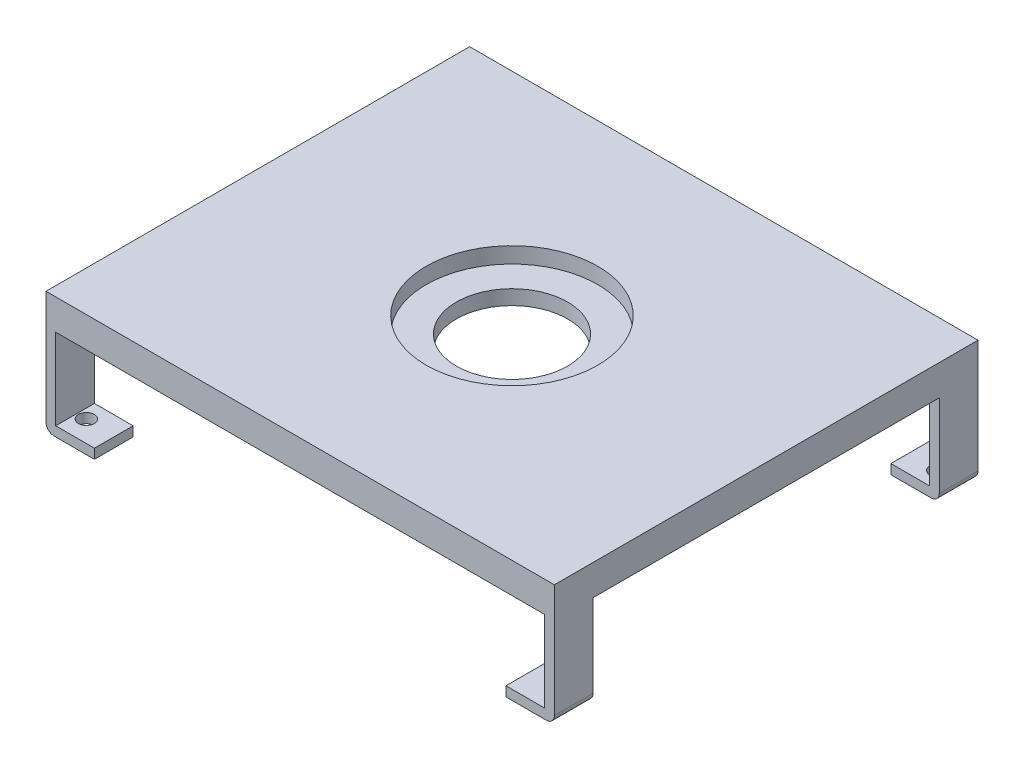
SolidWorks part; units mm, degrees
ref_plane "Plan de face" through (0, 0, 0) normal (0, 0, 1) x (1, 0, 0)
ref_plane "Plan de dessus" through (0, 0, 0) normal (0, 1, 0) x (1, 0, 0)
ref_plane "Plan de droite" through (0, 0, 0) normal (1, 0, 0) x (0, 0, -1)
sketch "Esquisse2" plane through (0, 0, 0) normal (0, 0, 1) x (1, 0, 0)
  line L0 (-64.77, 0) -> (-80.01, 0)
  line L1 (-80.01, 0) -> (-80.01, 36.2)
  line L2 (-80.01, 36.2) -> (80.01, 36.2)
  line L3 (80.01, 36.2) -> (80.01, 0)
  line L4 (80.01, 0) -> (64.77, 0)
  line L5 (64.77, 0) -> (64.77, 3.048)
  line L6 (64.77, 3.048) -> (76.962, 3.048)
  line L7 (76.962, 3.048) -> (76.962, 28.58)
  line L8 (76.962, 28.58) -> (-76.962, 28.58)
  line L9 (-76.962, 28.58) -> (-76.962, 3.048)
  line L10 (-76.962, 3.048) -> (-64.77, 3.048)
  line L11 (-64.77, 3.048) -> (-64.77, 0)
  point P12 (0, 36.2)
  dimension "D1" = 160.02
  dimension "D2" = 36.2
  dimension "D3" = 7.62
  dimension "D4" = 3.048
  dimension "D5" = 3.048
  dimension "D6" = 15.24
extrude "Boss.-Extru.1" add sketch "Esquisse2" along normal blind 133.35
sketch "Esquisse3" plane through (-80.01, 0, 0) normal (-1, 0, 0) x (0, 0, 1)
  line L0 (133.35, 0) -> (0, 0) construction
  line L1 (12.192, 0) -> (121.158, 0)
  line L2 (12.192, 0) -> (12.192, 28.58)
  line L3 (12.192, 28.58) -> (121.158, 28.58)
  line L4 (121.158, 0) -> (121.158, 28.58)
  line L5 (133.35, 36.2) -> (0, 36.2) construction
  line L6 (0, 36.2) -> (0, 0) construction
  line L7 (133.35, 36.2) -> (133.35, 0) construction
  dimension "D1" = 7.62
  dimension "D2" = 12.192
  dimension "D3" = 12.192
extrude "Enlèv. mat.-Extru.1" cut sketch "Esquisse3" against normal through all
fillet "Congé1" radius 2.54 4 edges at (-80.01, 0, 127.254) (-80.01, 0, 6.096) (80.01, 0, 127.254) (80.01, 0, 6.096)
ref_plane "Plane1" through (0, 0, 66.675) normal (0, 0, 1) x (1, 0, 0)
sketch "Sketch1" plane through (0, 36.2, 0) normal (0, 1, 0) x (1, 0, 0)
  line L1 (-80.01, 0) -> (80.01, 0)
  line L2 (-80.01, 0) -> (-80.01, -133.35)
  line L3 (-80.01, -133.35) -> (80.01, -133.35)
  line L4 (80.01, 0) -> (80.01, -133.35)
extrude "Boss-Extrude1" add sketch "Sketch1" along normal blind 2
sketch "Sketch2" plane through (0, 38.2, 0) normal (0, 1, 0) x (1, 0, 0)
  line L0 (-80.01, 0) -> (-80.01, -133.35) construction
  circle A0 centre (0, -66.675) radius 27
  circle A1 centre (0, -66.675) radius 17.5
  point P7 (-80.01, -66.675)
  dimension "D1" = 54
  dimension "D2" = 35
extrude "Cut-Extrude1" cut sketch "Sketch2" against normal through all contours A1 region at (0, 38.2, 66.675)
extrude "Cut-Extrude2" cut sketch "Sketch2<3>" against normal blind 5 contours A0 A1 region at (-26.2363, 38.2, 66.675)
sketch "Sketch2<3>" plane through (0, 38.2, 0) normal (0, 1, 0) x (1, 0, 0) same geometry as "Sketch2"
sketch "Sketch3" plane through (0, 0, 0) normal (0, -1, 0) x (1, 0, 0)
  line L0 (-74, 126.675) -> (74, 126.675) construction
  line L1 (74, 126.675) -> (74, 6.675) construction
  line L2 (74, 6.675) -> (-74, 6.675) construction
  line L3 (-74, 6.675) -> (-74, 126.675) construction
  line L4 (17.5, 66.675) -> (-17.5, 66.675) construction
  circle A0 centre (-74, 126.675) radius 2.5
  circle A1 centre (74, 126.675) radius 2.5
  circle A2 centre (74, 6.675) radius 2.5
  circle A3 centre (-74, 6.675) radius 2.5
  circle A4 centre (0, 66.675) radius 17.5 construction
  point P8 (0, 126.675)
  point P15 (0, 0)
  point P16 (-74, 66.675)
  dimension "D3" = 5
  dimension "D1" = 120
  dimension "D2" = 148
extrude "Cut-Extrude3" cut sketch "Sketch3" against normal blind 5
